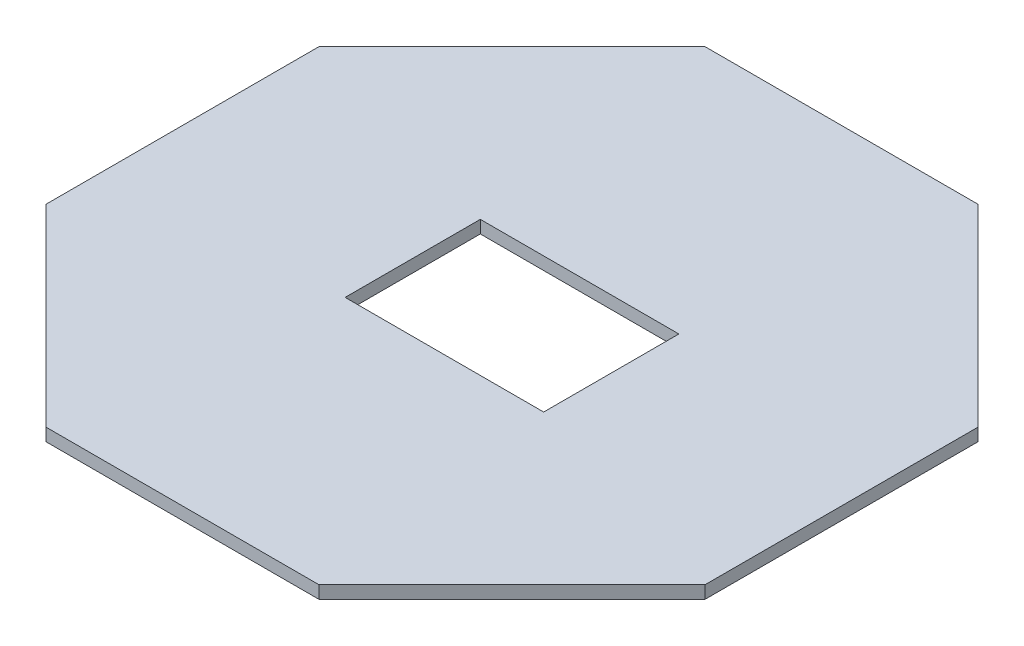
SolidWorks part; units mm, degrees
ref_plane "Front Plane" through (0, 0, 0) normal (0, 0, 1) x (1, 0, 0)
ref_plane "Top Plane" through (0, 0, 0) normal (0, 1, 0) x (1, 0, 0)
ref_plane "Right Plane" through (0, 0, 0) normal (1, 0, 0) x (0, 0, -1)
sketch "Sketch6" plane through (0, 0, 0) normal (0, 1, 0) x (1, 0, 0)
  line L1 (78, 32.3087) -> (32.3087, 78)
  line L2 (32.3087, 78) -> (-32.3087, 78)
  line L3 (-32.3087, 78) -> (-78, 32.3087)
  line L4 (-78, 32.3087) -> (-78, -32.3087)
  line L5 (-78, -32.3087) -> (-32.3087, -78)
  line L6 (-32.3087, -78) -> (32.3087, -78)
  line L7 (32.3087, -78) -> (78, -32.3087)
  line L8 (78, -32.3087) -> (78, 32.3087)
  circle A0 centre (0, 0) radius 78 construction
extrude "Boss-Extrude5" add sketch "Sketch6" against normal blind 3
sketch "Sketch9" plane through (0, 0, 0) normal (0, 1, 0) x (1, 0, 0)
  line L11 (-23.5, -16) -> (23.5, -16)
  line L12 (-23.5, -16) -> (-23.5, 16)
  line L13 (-23.5, 16) -> (23.5, 16)
  line L14 (23.5, -16) -> (23.5, 16)
  line L15 (-23.5, -16) -> (23.5, 16) construction
  line L16 (-23.5, 16) -> (23.5, -16) construction
  line L18 (75, -31.066) -> (75, 31.066)
  line L19 (75, 31.066) -> (31.066, 75)
  line L20 (31.066, 75) -> (-31.066, 75)
  line L21 (-31.066, 75) -> (-75, 31.066)
  line L22 (-75, 31.066) -> (-75, -31.066)
  line L23 (-75, -31.066) -> (-31.066, -75)
  line L24 (-31.066, -75) -> (31.066, -75)
  line L25 (31.066, -75) -> (75, -31.066)
  line L26 (75, -31.066) -> (75, 31.066) construction
  line L27 (75, 31.066) -> (31.066, 75) construction
  line L28 (31.066, 75) -> (-31.066, 75) construction
  line L29 (-31.066, 75) -> (-75, 31.066) construction
  line L30 (-75, 31.066) -> (-75, -31.066) construction
  line L31 (-75, -31.066) -> (-31.066, -75) construction
  line L32 (-31.066, -75) -> (31.066, -75) construction
  line L33 (31.066, -75) -> (75, -31.066) construction
  point P0 (0, 0)
  dimension "D2" = 47
  dimension "D3" = 32
  dimension "D1" = 3
extrude "Cut-Extrude1" cut sketch "Sketch9" against normal blind 3
